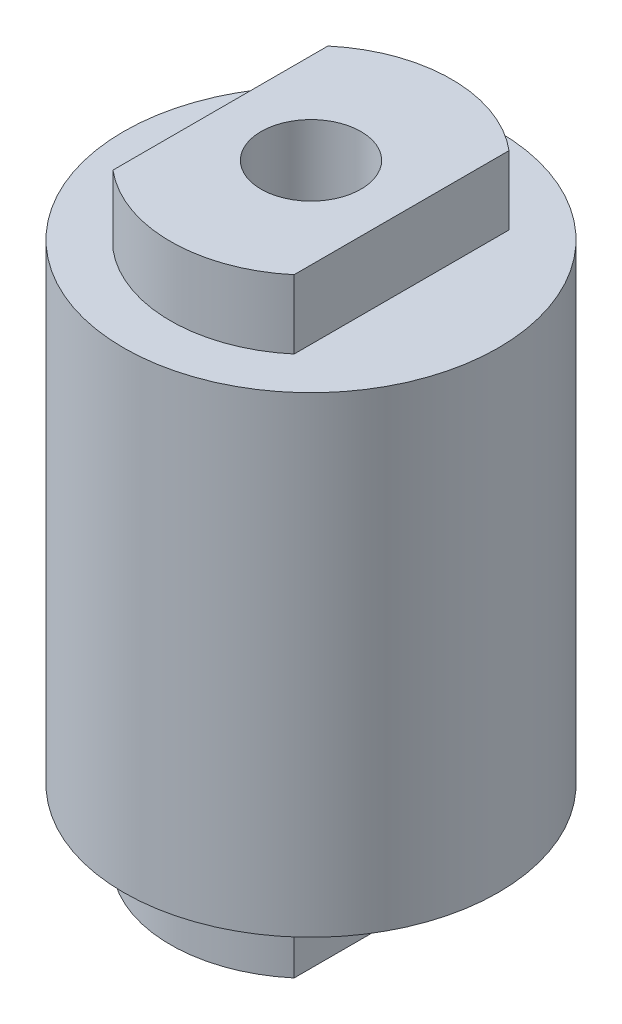
SolidWorks part; units mm, degrees
ref_plane "Front Plane" through (0, 0, 0) normal (0, 0, 1) x (1, 0, 0)
ref_plane "Top Plane" through (0, 0, 0) normal (0, 1, 0) x (1, 0, 0)
ref_plane "Right Plane" through (0, 0, 0) normal (1, 0, 0) x (0, 0, -1)
sketch "Sketch1" plane through (0, 0, 0) normal (0, 0, 1) x (1, 0, 0)
  line L0 (0, 9.75) -> (0, -9.75)
  line L5 (0, -9.75) -> (4.5, -9.75)
  line L6 (4.5, -9.75) -> (4.5, 9.75)
  line L7 (4.5, 9.75) -> (0, 9.75)
  point P3 (0, 0)
  dimension "D1" = 19.5
  dimension "D2" = 4.5
revolve "Revolve1" add sketch "Sketch1" angle 360 about L0
sketch "Sketch2" plane through (0, 9.75, 0) normal (0, 1, 0) x (1, 0, 0)
  line L0 (-2.9, 3.4409) -> (-2.9, -3.4409)
  line L1 (2.9, 3.4409) -> (2.9, -3.4409)
  line L2 (0, 0) -> (0, -1.5118) construction
  circle A0 centre (0, 0) radius 4.5 construction
  circle A1 centre (0, 0) radius 4.5
  circle A2 centre (0, 0) radius 6
  circle M3 centre (0, 0) radius 4.5
  dimension "D2" = 12
  dimension "D1" = 5.8
extrude "Cut-Extrude1" cut sketch "Sketch2" against normal blind 2.2 contours L0 M3 | L1 M3 region at (-3.5509, 9.75, 0) region at (3.5509, 9.75, 0)
sketch "Sketch5" plane through (0, 9.75, 0) normal (0, 1, 0) x (1, 0, 0)
  circle A0 centre (0, 0) radius 1.6
  dimension "D1" = 3.2
extrude "Cut-Extrude2" cut sketch "Sketch5" against normal through all contours A0
sketch "Sketch6" plane through (0, 9.75, 0) normal (0, 1, 0) x (1, 0, 0)
  line L1 (1.7032, 2.95) -> (-1.7032, 2.95)
  line L2 (-1.7032, 2.95) -> (-3.4064, 0)
  line L3 (-3.4064, 0) -> (-1.7032, -2.95)
  line L4 (-1.7032, -2.95) -> (1.7032, -2.95)
  line L5 (1.7032, -2.95) -> (3.4064, 0)
  line L6 (3.4064, 0) -> (1.7032, 2.95)
  line L8 (-1.7032, 2.95) -> (-6.7032, 2.95)
  line L9 (-1.7032, 2.95) -> (-1.7032, -2.95)
  line L10 (-1.7032, -2.95) -> (-6.7032, -2.95)
  line L11 (-6.7032, 2.95) -> (-6.7032, -2.95)
  circle A0 centre (0, 0) radius 2.95 construction
  circle M3 centre (0, 0) radius 1.6
  line M4 (-2.9, 3.4409) -> (-2.9, -3.4409)
  line M6 (2.9, -3.4409) -> (2.9, 3.4409)
  dimension "D1" = 5.9
  dimension "D2" = 5
extrude "Cut-Extrude3" cut sketch "Sketch6" along normal blind 2.65 from offset 7 contours L1 L9 L4 L5 L6 M3 M6 | L9 L2 L3 M4 M3 | L2 L3 M4 | L5 L6 M6 region at (2.2368, 9.75, -1.8761) region at (-2.1935, 9.75, 0) region at (3.0688, 9.75, 0) region at (-3.0688, 9.75, 0) offset against normal yes
mirror "Mirror2" about plane through (0, 0, 0) normal (0, 1, 0) of "Cut-Extrude3", "Cut-Extrude1", "Cut-Extrude2"
extrude "Boss-Extrude1" add sketch "Sketch2<3>" against normal up to surface (17.3 mm away) from surface contours A2 M3 region at (-5.8303, 9.75, 0) up to face at (-3.7, -7.55, 0) starting at face at (-3.7, 7.55, 0)
sketch "Sketch2<3>" plane through (0, 9.75, 0) normal (0, 1, 0) x (1, 0, 0) same geometry as "Sketch2"
equation "\"hole_depth\"=9"
equation "\"D1\"= \"hole_depth\""
equation "\"D19@Cut-Extrude3\"=\"hole_depth\"-2"
